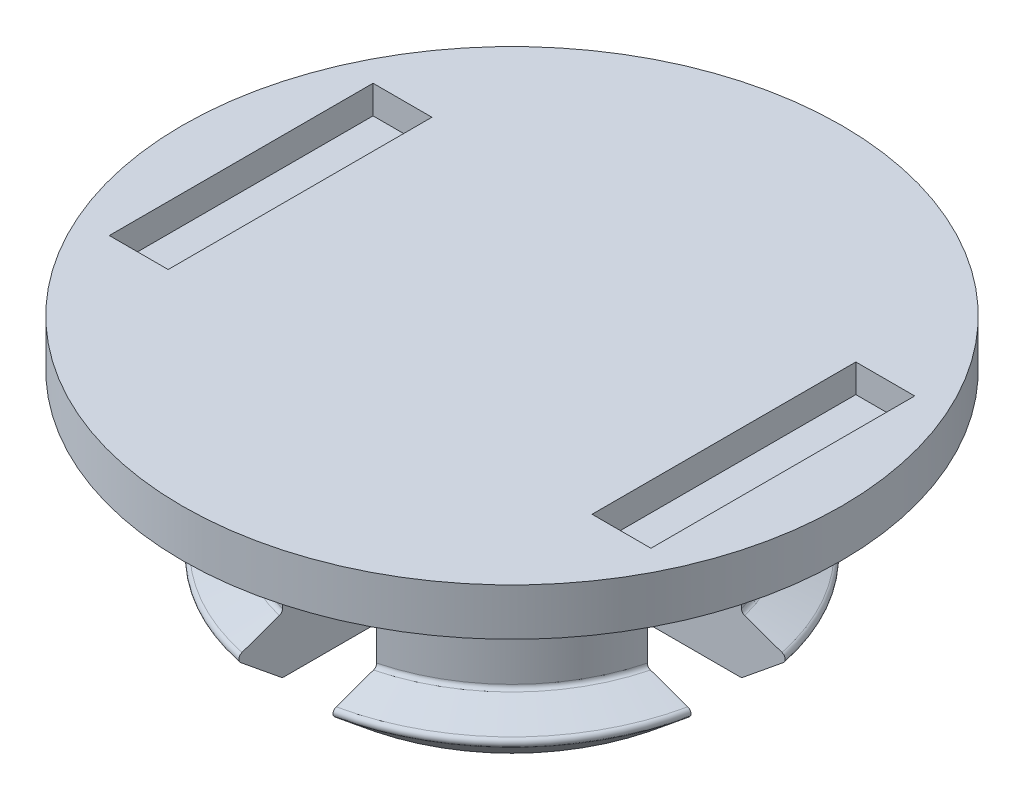
SolidWorks part; units mm, degrees
ref_plane "Front Plane" through (0, 0, 0) normal (0, 0, 1) x (1, 0, 0)
ref_plane "Top Plane" through (0, 0, 0) normal (0, 1, 0) x (1, 0, 0)
ref_plane "Right Plane" through (0, 0, 0) normal (1, 0, 0) x (0, 0, -1)
sketch "Szkic1" plane through (0, 0, 0) normal (0, 1, 0) x (1, 0, 0)
  circle A0 centre (0, 0) radius 7
  dimension "D1" = 14
extrude "Dodanie-wyciągnięcie1" add sketch "Szkic1" along normal blind 1
ref_point "Punkt1"
ref_plane "Płaszczyzna1" through (0, 0, 0) normal (0, -1, 0) x (-1, 0, 0)
sketch "Szkic2" plane through (0, 0, 0) normal (0, -1, 0) x (-1, 0, 0)
  circle A0 centre (0, 0) radius 4
  dimension "D1" = 8
extrude "Dodanie-wyciągnięcie2" add sketch "Szkic2" along normal blind 4.22
ref_axis "Oś1" through (0, -4.22, 0) along (0, 1, 0)
sketch "Szkic3" plane through (0, 0, 0) normal (1, 0, 0) x (0, 0, -1)
  line L1 (4, -4.22) -> (5, -3.384)
  line L2 (5, -3.384) -> (4, -3.02)
  line L4 (4, -3.02) -> (4, -4.22)
  line L5 (0, -4.22) -> (0, 0) construction
  line L7 (-7.7, 0) -> (7.7, 0) construction
  dimension "D1" = 4
  dimension "D2" = 1.2
  dimension "D3" = 70
  dimension "D4" = 4.22
  dimension "D5" = 5
revolve "Obrót1" add sketch "Szkic3" angle 360 about axis through (0, -4.22, 0) along (0, 1, 0)
fillet "Zaokrąglenie1" radius 0.1 3 edges at (0, -3.384, -5) (0, -3.02, -4) (0, -4.22, -4)
ref_plane "Płaszczyzna2" through (0, -4.22, 0) normal (0, -1, 0) x (-1, 0, 0)
sketch "Szkic5" plane through (0, -4.22, 0) normal (0, -1, 0) x (-1, 0, 0)
  line L0 (-7.7941, -1) -> (-1, -1)
  line L1 (7.7941, 1) -> (1, 1)
  line L2 (-1, -7.7941) -> (-1, -1)
  line L3 (1, 7.7941) -> (1, 1)
  line L4 (-1, 1) -> (-1, 7.7941)
  line L5 (1, -1) -> (7.7941, -1)
  line L6 (1, -1) -> (1, -7.7941)
  line L7 (-1, 1) -> (-7.7941, 1)
  line L8 (-1, -1) -> (1, 1) construction
  arc A0 (-7.7941, 1) -> (-7.7941, -1) centre (0, 0) ccw
  arc A1 (-1, -7.7941) -> (1, -7.7941) centre (0, 0) ccw
  arc A2 (7.7941, -1) -> (7.7941, 1) centre (0, 0) ccw
  arc A3 (1, 7.7941) -> (-1, 7.7941) centre (0, 0) ccw
  point P1 (0, 0)
  dimension "D1" = 2
  dimension "D2" = 2
extrude "Wytnij-wyciągnięcie1" cut sketch "Szkic5" against normal blind 4.22
ref_plane "Płaszczyzna3" through (0, 1, 0) normal (0, 1, 0) x (1, 0, 0)
sketch "Szkic8" plane through (0, 1, 0) normal (0, 1, 0) x (1, 0, 0)
  line L0 (4.5, -2.8) -> (-4.5, 2.8) construction
  line L1 (5.75, -2.8) -> (4.5, -2.8)
  line L2 (5.75, -2.8) -> (5.75, 2.8)
  line L3 (5.75, 2.8) -> (4.5, 2.8)
  line L4 (4.5, -2.8) -> (4.5, 2.8)
  line L5 (-4.5, -2.8) -> (-5.75, -2.8)
  line L6 (-4.5, -2.8) -> (-4.5, 2.8)
  line L7 (-4.5, 2.8) -> (-5.75, 2.8)
  line L8 (-5.75, -2.8) -> (-5.75, 2.8)
  point P8 (0, 0)
  dimension "D1" = 5.6
  dimension "D2" = 1.25
  dimension "D3" = 9
extrude "Wytnij-wyciągnięcie2" cut sketch "Szkic8" against normal blind 0.6
